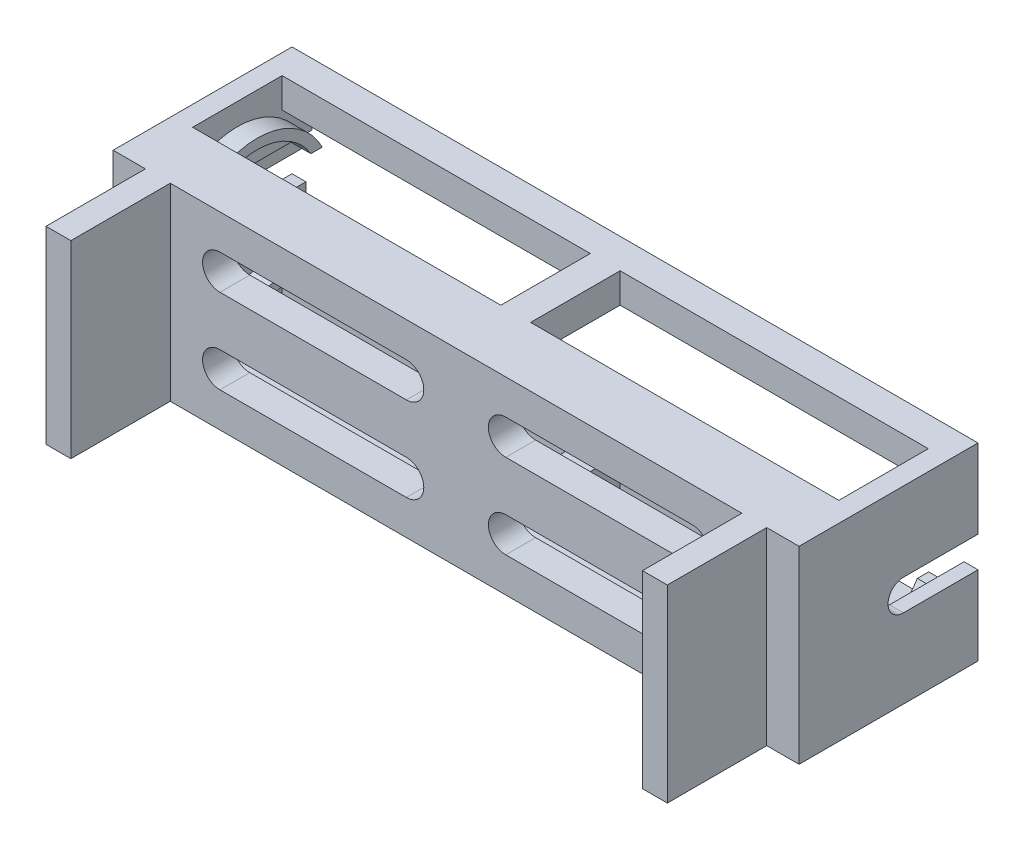
SolidWorks part; units mm, degrees
ref_plane "Plano frontal" through (0, 0, 0) normal (0, 0, 1) x (1, 0, 0)
ref_plane "Plano superior" through (0, 0, 0) normal (0, 1, 0) x (1, 0, 0)
ref_plane "Plano direito" through (0, 0, 0) normal (1, 0, 0) x (0, 0, -1)
sketch "Esboço1" plane through (0, 0, 0) normal (0, 0, 1) x (1, 0, 0)
  line L1 (32.5, -19) -> (-32.5, -19)
  line L2 (32.5, -19) -> (32.5, 19)
  line L3 (32.5, 19) -> (-32.5, 19)
  line L4 (-32.5, -19) -> (-32.5, 19)
  line L5 (32.5, -19) -> (-32.5, 19) construction
  line L6 (32.5, 19) -> (-32.5, -19) construction
  point P0 (0, 0)
  dimension "D1" = 65
  dimension "D2" = 38
extrude "Ressalto-extrusão1" add sketch "Esboço1" along normal blind 6
sketch "Esboço2" plane through (-32.5, 0, 0) normal (-1, 0, 0) x (0, 0, 1)
  line L0 (0, 19) -> (-30, 19)
  line L1 (-30, 19) -> (-30, -19)
  line L2 (-30, -19) -> (0, -19)
  line L4 (0, 19) -> (0, -19)
  line L5 (0, -19) -> (6, -19)
  line L6 (6, -19) -> (6, 19)
  line L7 (6, 19) -> (0, 19)
  line L8 (0, 19) -> (0, -19) construction
  line L9 (0, -19) -> (6, -19)
  line L10 (6, -19) -> (6, 19)
  line L11 (6, 19) -> (0, 19)
  dimension "D2" = 30
  dimension "D1" = 0
extrude "Ressalto-extrusão2" add sketch "Esboço2" along normal blind 4
sketch "Esboço3" plane through (-36.5, 0, 0) normal (-1, 0, 0) x (0, 0, 1)
  line L0 (0, 19) -> (0, -19) construction
  line L1 (0, 19) -> (0, -19) construction
  line L2 (-15, 3.1) -> (-30, 3.1)
  line L3 (0, 19) -> (-30, 19) construction
  line L4 (0, 19) -> (0, -19) construction
  line L5 (0, -19) -> (-30, -19) construction
  line L6 (-30, 19) -> (-30, -19) construction
  line L7 (-15, -19) -> (-15, 19) construction
  line L8 (0, 0) -> (-30, 0) construction
  line L9 (-30, 3.1) -> (-30, -3.1)
  line L10 (-30, -3.1) -> (-15, -3.1)
  arc A0 (-15, -3.1) -> (-15, 3.1) centre (-15, 0) ccw
  point P276 (-15, 0)
  dimension "D1" = 6.2
extrude "Corte-extrusão1" cut sketch "Esboço3" against normal through all
sketch "Esboço5" plane through (0, 0, 6) normal (0, 0, 1) x (1, 0, 0)
  line L0 (-36.5, -19) -> (32.5, -19) construction
  line L1 (-36.5, 19) -> (-30, 19)
  line L2 (-36.5, 19) -> (-36.5, -19)
  line L3 (-36.5, -19) -> (-30, -19)
  line L4 (-30, 19) -> (-30, -19)
  line L6 (-30, 19) -> (-25, 19)
  line L7 (-30, 19) -> (-30, -19)
  line L8 (-30, -19) -> (-25, -19)
  line L9 (-25, 19) -> (-25, -19)
  line L10 (-25, 19) -> (-21.5, 19)
  line L11 (-25, 19) -> (-25, -19)
  line L12 (-25, -19) -> (-21.5, -19)
  line L13 (-21.5, 19) -> (-21.5, -19)
  line M5 (32.5, 19) -> (-36.5, 19)
  line M7 (-36.5, -19) -> (32.5, -19)
  dimension "D1" = 15
  dimension "D2" = 6.5
  dimension "D3" = 5
extrude "Ressalto-extrusão4" add sketch "Esboço5" along normal blind 20 contours L9 L4 M5 M7 region at (-27.5, 0, 6)
sketch "Esboço7" plane through (-32.5, 0, 0) normal (1, 0, 0) x (0, 0, -1)
  line L0 (15, -6.5) -> (30, -6.5)
  line L1 (30, -3.1) -> (30, -19) construction
  line L2 (30, -6.5) -> (30, 6.5)
  line L3 (30, 19) -> (30, 3.1) construction
  line L4 (30, 6.5) -> (15, 6.5)
  arc A0 (15, 6.5) -> (15, -6.5) centre (15, 0) ccw
  dimension "D1" = 13
extrude "Corte-extrusão3" cut sketch "Esboço7" against normal blind 1.2
sketch "Esboço8" plane through (-32.5, 0, 0) normal (1, 0, 0) x (0, 0, -1)
  line L4 (15, -6.5) -> (30, -6.5) construction
  line L5 (25.794, -6.5) -> (28.0733, -6.5)
  line L6 (30, 6.5) -> (15, 6.5) construction
  line L7 (28.0733, 6.5) -> (25.794, 6.5)
  arc A0 (25.794, 6.5) -> (25.794, -6.5) centre (15, 0) ccw
  arc A1 (28.0733, 6.5) -> (28.0733, -6.5) centre (15, 0) ccw
  dimension "D1" = 25.2
  dimension "D2" = 2
extrude "Ressalto-extrusão5" add sketch "Esboço8" along normal blind 4
sketch "Esboço11" plane through (0, 0, 6) normal (0, 0, 1) x (1, 0, 0)
  line L0 (-15, 8.5) -> (22.5, 8.5) construction
  line L1 (-15, 12) -> (22.5, 12)
  line L2 (-15, 5) -> (22.5, 5)
  line L3 (-15, -8.5) -> (22.5, -8.5) construction
  line L4 (-15, -5) -> (22.5, -5)
  line L5 (-15, -12) -> (22.5, -12)
  line L6 (32.5, -19) -> (32.5, 19) construction
  line L7 (-25, 19) -> (-25, -19) construction
  line L8 (32.5, 19) -> (-25, 19) construction
  line L9 (-25, -19) -> (32.5, -19) construction
  line L10 (3.75, 19) -> (3.75, -19) construction
  arc A0 (-15, 12) -> (-15, 5) centre (-15, 8.5) ccw
  arc A1 (22.5, 5) -> (22.5, 12) centre (22.5, 8.5) ccw
  arc A2 (-15, -5) -> (-15, -12) centre (-15, -8.5) ccw
  arc A3 (22.5, -12) -> (22.5, -5) centre (22.5, -8.5) ccw
  point P2 (3.75, 8.5)
  point P7 (3.75, -8.5)
  point P22 (-18.6478, -6)
  point P23 (0, 0)
  dimension "D1" = 10
  dimension "D2" = 10
  dimension "D3" = 7
  dimension "D4" = 7
  dimension "D5" = 10
extrude "Corte-extrusão4" cut sketch "Esboço11" against normal through all
sketch "Esboço12" plane through (-32.5, 0, 0) normal (1, 0, 0) x (0, 0, -1)
  line L14 (0, -19) -> (6, -19)
  line L15 (0, -19) -> (0, -13)
  line L16 (0, -13) -> (6, -13)
  line L17 (6, -19) -> (6, -13)
  line L18 (30, -19) -> (24, -19)
  line L19 (30, -19) -> (30, -13)
  line L20 (30, -13) -> (24, -13)
  line L21 (24, -19) -> (24, -13)
  point P6 (21.6717, -10.6887)
  point P7 (0, 0)
  point P8 (5.9251, -13.0749)
  point P13 (6.8718, -12.1282)
  point P14 (6.8718, -12.1282)
  point P15 (8.3074, -10.6756)
  point P16 (24.4986, -13.4986)
  point P19 (23.1282, -12.1282)
  point P20 (23.1282, -12.1282)
  point P21 (0, 0)
  dimension "D1" = 6
  dimension "D2" = 6
extrude "Ressalto-extrusão6" add sketch "Esboço12" along normal up to surface (65 mm away) up to face at (32.5, 0, 3)
sketch "Esboço13" plane through (0, 0, -24) normal (0, 0, 1) x (1, 0, 0)
  line L0 (32.5, -13) -> (-32.5, -13) construction
  line L1 (32.5, -19) -> (29.5, -19)
  line L2 (32.5, -19) -> (32.5, -13)
  line L3 (32.5, -13) -> (29.5, -13)
  line L4 (29.5, -19) -> (29.5, -13)
  dimension "D1" = 3
extrude "Ressalto-extrusão7" add sketch "Esboço13" along normal up to surface (18 mm away) up to face at (0, -16, -6)
ref_plane "Plano1" through (0, 0, 0) normal (0, 1, 0) x (1, 0, 0)
sketch "Esboço14" plane through (0, 0, -24) normal (0, 0, 1) x (1, 0, 0)
  line L0 (29.5, -13) -> (-32.5, -13) construction
  line L1 (-4.5, -13) -> (1.5, -13)
  line L2 (-4.5, -13) -> (-4.5, -19)
  line L3 (-4.5, -19) -> (1.5, -19)
  line L4 (1.5, -13) -> (1.5, -19)
  line L5 (29.5, -19) -> (-32.5, -19) construction
  line L6 (-4.5, -16) -> (-32.5, -16) construction
  line L7 (-32.5, -13) -> (-32.5, -19) construction
  line L8 (1.5, -16) -> (29.5, -16) construction
  line L9 (29.5, -13) -> (29.5, -19) construction
mirror "Espelhar2" about plane through (0, 0, 0) normal (0, 1, 0) of "Ressalto-extrusão6", "Ressalto-extrusão7"
mirror "Espelhar1" about plane through (32.5, -19, 6) normal (-1, 0, 0) of "Corte-extrusão4", "Corte-extrusão1", "Ressalto-extrusão4", "Ressalto-extrusão2", "Ressalto-extrusão1", "Corte-extrusão3", "Ressalto-extrusão5", "Ressalto-extrusão6", "Ressalto-extrusão7", "Espelhar2"
